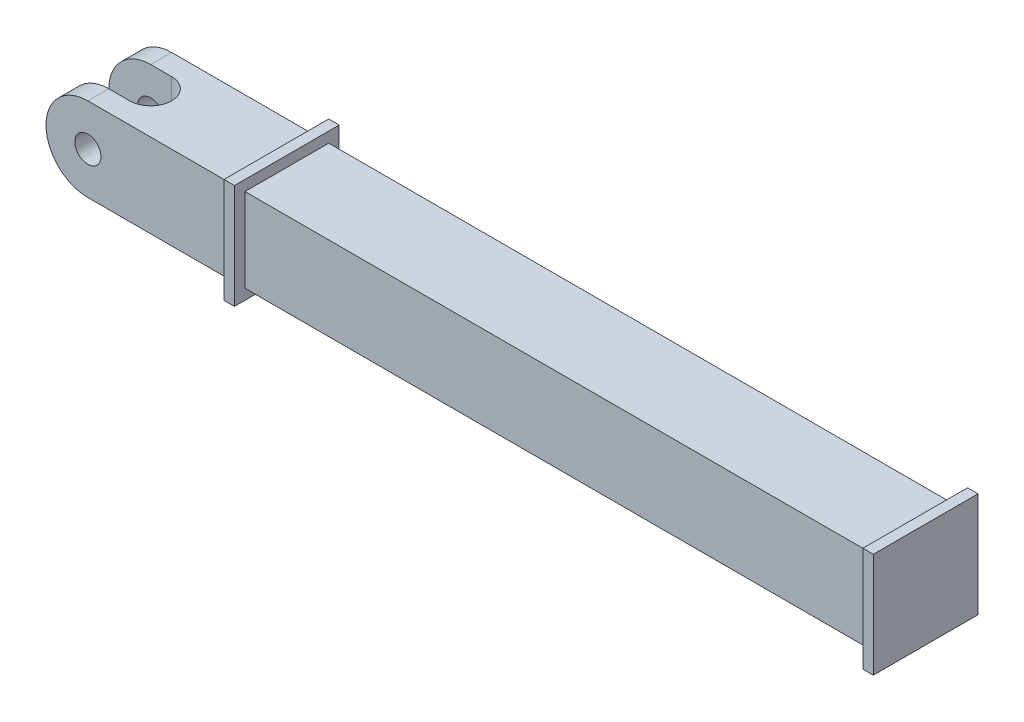
SolidWorks part; units mm, degrees
ref_plane "Front Plane" through (0, 0, 0) normal (0, 0, 1) x (1, 0, 0)
ref_plane "Top Plane" through (0, 0, 0) normal (0, 1, 0) x (1, 0, 0)
ref_plane "Right Plane" through (0, 0, 0) normal (1, 0, 0) x (0, 0, -1)
sketch "Sketch1" plane through (0, 0, 0) normal (0, 1, 0) x (1, 0, 0)
  line L1 (-330, -40) -> (330, -40)
  line L2 (-330, -40) -> (-330, 40)
  line L3 (-330, 40) -> (330, 40)
  line L4 (330, -40) -> (330, 40)
  line L5 (-330, -40) -> (330, 40) construction
  line L6 (-330, 40) -> (330, -40) construction
  point P0 (0, 0)
  dimension "D1" = 80
  dimension "D2" = 660
extrude "Boss-Extrude1" add sketch "Sketch1" along normal blind 80
sketch "Sketch2" plane through (0, 0, 0) normal (1, 0, 0) x (0, 0, -1)
  line L0 (40, 80) -> (40, 0) construction
  line L1 (-40, 0) -> (40, 0) construction
  line L2 (-40, 80) -> (-40, 0) construction
  line L3 (-40, 80) -> (40, 80) construction
  line L4 (40, 80) -> (40, 0)
  line L5 (-40, 0) -> (40, 0)
  line L6 (-40, 80) -> (-40, 0)
  line L7 (-40, 80) -> (40, 80)
  line L8 (-50, -10) -> (50, -10)
  line L9 (50, 90) -> (50, -10)
  line L10 (-50, 90) -> (50, 90)
  line L11 (-50, 90) -> (-50, -10)
  dimension "D1" = 10
extrude "Boss-Extrude2" add sketch "Sketch2" along direction (-1, 0, 0) on the side of the normal blind 10 from offset 320 contours L11 L8 L9 L10
extrude "Boss-Extrude3" add sketch "Sketch2<2>" against normal blind 10 from offset 280 contours L11 L8 L9 L10 offset against normal yes
sketch "Sketch2<2>" plane through (0, 0, 0) normal (1, 0, 0) x (0, 0, -1) same geometry as "Sketch2"
extrude "Boss-Extrude4" add sketch "Sketch2<4>" against normal blind 100 from surface contours L6 L5 L4 L7 starting at face at (-290, 40, 0)
sketch "Sketch2<4>" plane through (0, 0, 0) normal (1, 0, 0) x (0, 0, -1) same geometry as "Sketch2"
sketch "Sketch4" plane through (0, 0, 40) normal (0, 0, 1) x (1, 0, 0)
  line L0 (-390, 0) -> (-390, 80) construction
  line L1 (-390, 0) -> (-390, 80)
  line L2 (-430, 40) -> (-390, 40) construction
  line L3 (-390, 0) -> (-430, 0)
  line L4 (-430, 0) -> (-430, 80)
  line L5 (-430, 80) -> (-390, 80)
  line L6 (-470, 40) -> (-430, 40) construction
  arc A3 (-430, 80) -> (-430, 0) centre (-430, 40) ccw
  circle A4 centre (-430, 40) radius 12.5
  point P0 (-390, 40)
  line M3 (-390, 80) -> (-390, 0)
  dimension "D1" = 40
  dimension "D2" = 25
extrude "Boss-Extrude5" add sketch "Sketch4" against normal up to surface (80 mm away) contours A4 L4 A3 | A4 L4 L3 L5 M3 region at (-408.7793, 40, 40) region at (-448.2397, 40, 40) up to face at (-340, 40, -40)
sketch "Sketch5" plane through (0, 80, 0) normal (0, 1, 0) x (1, 0, 0)
  line L1 (-430, 40) -> (-430, -40) construction
  line L2 (-470, 40) -> (-470, -40) construction
  line L3 (-430, 40) -> (-430, -40) construction
  line L4 (-470, 40) -> (-470, -40) construction
  line L9 (-470, 40) -> (-430, 40) construction
  line L10 (-470, -40) -> (-430, -40) construction
  line L11 (-470, 20) -> (-430, 20)
  line L12 (-470, -20) -> (-430, -20)
  line L13 (-450, 40) -> (-450, 20) construction
  line L14 (-450, -20) -> (-450, -40) construction
  line L15 (-430, 20) -> (-410, 20)
  line L16 (-470, 20) -> (-470, -20)
  line L17 (-410, 20) -> (-410, -20) construction
  line L18 (-410, -20) -> (-430, -20)
  arc A2 (-410, 20) -> (-410, -20) centre (-410, 0) cw
  point P15 (0, 0)
  point P16 (-410, 0)
  dimension "D1" = 20
  dimension "D2" = 20
extrude "Cut-Extrude1" cut sketch "Sketch5" against normal up to surface (80 mm away) contours L11 L15 A2 L18 L12 L16 up to face at (-360, 0, 0)
